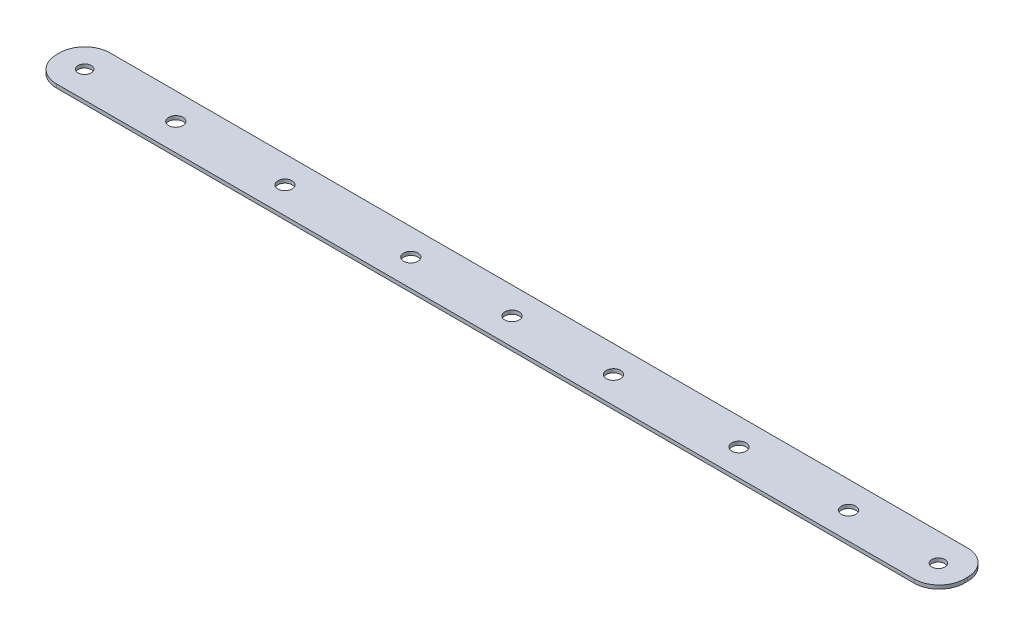
SolidWorks part; units mm, degrees
ref_plane "Front Plane" through (0, 0, 0) normal (0, 0, 1) x (1, 0, 0)
ref_plane "Top Plane" through (0, 0, 0) normal (0, 1, 0) x (1, 0, 0)
ref_plane "Right Plane" through (0, 0, 0) normal (1, 0, 0) x (0, 0, -1)
sketch "Sketch1" plane through (0, 0, 0) normal (0, 1, 0) x (1, 0, 0)
  line L1 (107.95, -6.375) -> (-107.95, -6.375)
  line L2 (107.95, -6.375) -> (107.95, 6.375)
  line L3 (107.95, 6.375) -> (-107.95, 6.375)
  line L4 (-107.95, -6.375) -> (-107.95, 6.375)
  line L5 (107.95, -6.375) -> (-107.95, 6.375) construction
  line L6 (107.95, 6.375) -> (-107.95, -6.375) construction
  circle A0 centre (-101.6, 0) radius 1.55
  point P0 (0, 0)
  dimension "D1" = 215.9
  dimension "D2" = 12.75
base flange "Base-Flange1" sketch "Sketch1" thickness 0.86 reverse thickness direction no parameters "D1"=0.7366
fillet "Fillet1" radius 6 4 edges at (107.95, -0.43, 6.375) (107.95, -0.43, -6.375) (-107.95, -0.43, -6.375) (-107.95, -0.43, 6.375)
ref_plane "Plane1" through (0, -0.86, 6.375) normal (-1, 0, 0) x (0, 0, 1)
hole_wizard "M3 Clearance Hole1" positions "Sketch11" profile "Sketch10" hole size "M3" standard "ANSI Metric"
sketch "Sketch11" plane through (0, 0, 0) normal (0, 1, 0) x (1, 0, 0)
  point P0 (-80.0116, 0.0752)
  point P2 (-24.1316, 0.0752)
  point P6 (80.01, 0)
  point P8 (24.13, 0)
  dimension "D1" = 27.94
  dimension "D2" = 55.88
  dimension "D3" = 55.88
  dimension "D4" = 187.96
sketch "Sketch10" plane through (-80.0116, 0, -0.0752) normal (1, 0, 0) x (0, 0, 1)
  line L0 (0, 0) -> (0, 2.3115)
  line L1 (0, 2.3115) -> (1.7, 1.29)
  line L2 (1.7, 1.29) -> (1.7, 0)
  line L5 (1.7, 0) -> (0, 0)
  line L10 (0, 2.3115) -> (-1.7, 1.29) construction
  line L11 (0, -6.35) -> (0, 107.95) construction
  dimension "Hole Dia." = 3.4
  dimension "Hole Depth" = 1.29
  dimension "Drill Angle" = 118
hole_wizard "M3 Clearance Hole2" positions "Sketch13" profile "Sketch12" hole size "M3" standard "ANSI Metric"
sketch "Sketch13" plane through (0, 0, 0) normal (0, 1, 0) x (1, 0, 0)
  point P0 (0, 0)
  point P3 (-53.975, 0)
  point P4 (53.975, 0)
  dimension "D1" = 53.975
  dimension "D2" = 53.975
sketch "Sketch12" plane through (0, 0, 0) normal (1, 0, 0) x (0, 0, 1)
  line L0 (0, 0) -> (0, 2.3115)
  line L1 (0, 2.3115) -> (1.7, 1.29)
  line L2 (1.7, 1.29) -> (1.7, 0)
  line L5 (1.7, 0) -> (0, 0)
  line L10 (0, 2.3115) -> (-1.7, 1.29) construction
  line L11 (0, -6.35) -> (0, 107.95) construction
  dimension "Hole Dia." = 3.4
  dimension "Hole Depth" = 1.29
  dimension "Drill Angle" = 118
sketch "Sketch14" plane through (0, 0, 0) normal (0, 1, 0) x (1, 0, 0)
  circle A0 centre (101.6014, -0.2424) radius 1.55
  dimension "D1" = 6.35
extrude "Cut-Extrude1" cut sketch "Sketch14" against normal blind 82 contours A0 normal cut yes
sketch "Bend-Lines1" [suppressed] plane through (0, 0, 0) normal (0, 1, 0) x (1, 0, 0)
sketch "Bounding-Box1" [suppressed] plane through (0, 0, 0) normal (0, 1, 0) x (1, 0, 0)
sheet metal parameters "Sheet-Metal(1)" thickness 0.86 parameters "D1"=0.7366
flat pattern "Flat-Pattern(1)" [suppressed]
sketch "Bend-Lines2" plane through (0, 0, 0) normal (0, 1, 0) x (1, 0, 0)
sketch "Bounding-Box2" [suppressed] plane through (0, 0, 0) normal (0, 1, 0) x (1, 0, 0)
sheet metal parameters "Sheet-Metal(2)" thickness 0.86 parameters "D1"=0.7366
flat pattern "Flat-Pattern(1)"
sketch "Bend-Lines2" plane through (0, 0, 0) normal (0, 1, 0) x (1, 0, 0)
sketch "Bounding-Box2" [suppressed] plane through (0, 0, 0) normal (0, 1, 0) x (1, 0, 0)
sheet metal parameters "Sheet-Metal(3)" thickness 0.86 parameters "D1"=0.7366
flat pattern "Flat-Pattern(1)"
sketch "Bend-Lines2" plane through (0, 0, 0) normal (0, 1, 0) x (1, 0, 0)
sketch "Bounding-Box2" [suppressed] plane through (0, 0, 0) normal (0, 1, 0) x (1, 0, 0)
sheet metal parameters "Sheet-Metal(4)" thickness 0.86 parameters "D1"=0.7366
flat pattern "Flat-Pattern(1)"
sketch "Bend-Lines2" plane through (0, 0, 0) normal (0, 1, 0) x (1, 0, 0)
sketch "Bounding-Box2" [suppressed] plane through (0, 0, 0) normal (0, 1, 0) x (1, 0, 0)
